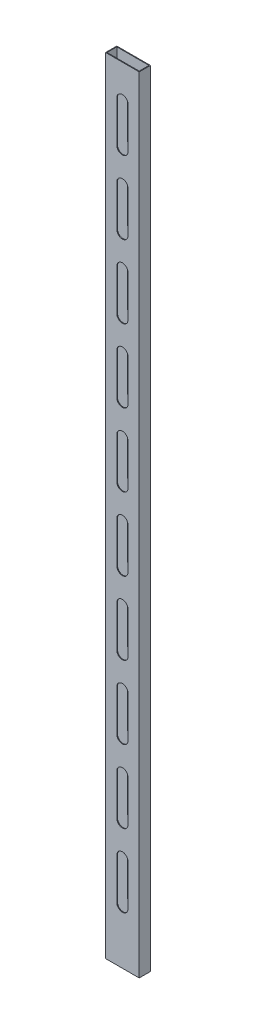
SolidWorks part; units mm, degrees
ref_plane "Front Plane" through (0, 0, 0) normal (0, 0, 1) x (1, 0, 0)
ref_plane "Top Plane" through (0, 0, 0) normal (0, 1, 0) x (1, 0, 0)
ref_plane "Right Plane" through (0, 0, 0) normal (1, 0, 0) x (0, 0, -1)
sketch "Sketch1" plane through (0, 0, 0) normal (0, 1, 0) x (1, 0, 0)
  line L1 (0, 0) -> (-76.2, 0)
  line L2 (0, 0) -> (0, 25.4)
  line L3 (0, 25.4) -> (-76.2, 25.4)
  line L4 (-76.2, 0) -> (-76.2, 25.4)
  line L5 (-74.6125, 1.5875) -> (-1.5875, 1.5875)
  line L6 (-74.6125, 1.5875) -> (-74.6125, 23.8125)
  line L7 (-74.6125, 23.8125) -> (-1.5875, 23.8125)
  line L8 (-1.5875, 1.5875) -> (-1.5875, 23.8125)
  dimension "D1" = 76.2
  dimension "D2" = 25.4
  dimension "D3" = 1.5875
  dimension "D4" = 1.5875
  dimension "D5" = 1.5875
  dimension "D6" = 1.5875
extrude "Boss-Extrude1" add sketch "Sketch1" along normal blind 1778
sketch "Sketch2" plane through (0, 0, 0) normal (0, 0, 1) x (1, 0, 0)
  line L0 (-38.1, 1701.8) -> (-38.1, 1608.6977) construction
  line L1 (-25.4, 1701.8) -> (-25.4, 1608.6977)
  line L2 (-50.8, 1701.8) -> (-50.8, 1608.6977)
  line L3 (0, 1778) -> (0, 0) construction
  line L4 (-76.2, 1778) -> (0, 1778) construction
  line L5 (-38.1, 1536.7) -> (-38.1, 1443.5977) construction
  line L6 (-25.4, 1536.7) -> (-25.4, 1443.5977)
  line L7 (-50.8, 1536.7) -> (-50.8, 1443.5977)
  line L8 (-38.1, 1371.6) -> (-38.1, 1278.4977) construction
  line L9 (-25.4, 1371.6) -> (-25.4, 1278.4977)
  line L10 (-50.8, 1371.6) -> (-50.8, 1278.4977)
  line L11 (-38.1, 1206.5) -> (-38.1, 1113.3977) construction
  line L12 (-25.4, 1206.5) -> (-25.4, 1113.3977)
  line L13 (-50.8, 1206.5) -> (-50.8, 1113.3977)
  line L14 (-38.1, 1041.4) -> (-38.1, 948.2977) construction
  line L15 (-25.4, 1041.4) -> (-25.4, 948.2977)
  line L16 (-50.8, 1041.4) -> (-50.8, 948.2977)
  line L17 (-38.1, 876.3) -> (-38.1, 783.1977) construction
  line L18 (-25.4, 876.3) -> (-25.4, 783.1977)
  line L19 (-50.8, 876.3) -> (-50.8, 783.1977)
  line L20 (-38.1, 711.2) -> (-38.1, 618.0977) construction
  line L21 (-25.4, 711.2) -> (-25.4, 618.0977)
  line L22 (-50.8, 711.2) -> (-50.8, 618.0977)
  line L23 (-38.1, 546.1) -> (-38.1, 452.9977) construction
  line L24 (-25.4, 546.1) -> (-25.4, 452.9977)
  line L25 (-50.8, 546.1) -> (-50.8, 452.9977)
  line L26 (-38.1, 381) -> (-38.1, 287.8977) construction
  line L27 (-25.4, 381) -> (-25.4, 287.8977)
  line L28 (-50.8, 381) -> (-50.8, 287.8977)
  line L29 (-38.1, 215.9) -> (-38.1, 122.7977) construction
  line L30 (-25.4, 215.9) -> (-25.4, 122.7977)
  line L31 (-50.8, 215.9) -> (-50.8, 122.7977)
  arc A0 (-25.4, 1701.8) -> (-50.8, 1701.8) centre (-38.1, 1701.8) ccw
  arc A1 (-50.8, 1608.6977) -> (-25.4, 1608.6977) centre (-38.1, 1608.6977) ccw
  arc A2 (-25.4, 1536.7) -> (-50.8, 1536.7) centre (-38.1, 1536.7) ccw
  arc A3 (-50.8, 1443.5977) -> (-25.4, 1443.5977) centre (-38.1, 1443.5977) ccw
  arc A4 (-25.4, 1371.6) -> (-50.8, 1371.6) centre (-38.1, 1371.6) ccw
  arc A5 (-50.8, 1278.4977) -> (-25.4, 1278.4977) centre (-38.1, 1278.4977) ccw
  arc A6 (-25.4, 1206.5) -> (-50.8, 1206.5) centre (-38.1, 1206.5) ccw
  arc A7 (-50.8, 1113.3977) -> (-25.4, 1113.3977) centre (-38.1, 1113.3977) ccw
  arc A8 (-25.4, 1041.4) -> (-50.8, 1041.4) centre (-38.1, 1041.4) ccw
  arc A9 (-50.8, 948.2977) -> (-25.4, 948.2977) centre (-38.1, 948.2977) ccw
  arc A10 (-25.4, 876.3) -> (-50.8, 876.3) centre (-38.1, 876.3) ccw
  arc A11 (-50.8, 783.1977) -> (-25.4, 783.1977) centre (-38.1, 783.1977) ccw
  arc A12 (-25.4, 711.2) -> (-50.8, 711.2) centre (-38.1, 711.2) ccw
  arc A13 (-50.8, 618.0977) -> (-25.4, 618.0977) centre (-38.1, 618.0977) ccw
  arc A14 (-25.4, 546.1) -> (-50.8, 546.1) centre (-38.1, 546.1) ccw
  arc A15 (-50.8, 452.9977) -> (-25.4, 452.9977) centre (-38.1, 452.9977) ccw
  arc A16 (-25.4, 381) -> (-50.8, 381) centre (-38.1, 381) ccw
  arc A17 (-50.8, 287.8977) -> (-25.4, 287.8977) centre (-38.1, 287.8977) ccw
  arc A18 (-25.4, 215.9) -> (-50.8, 215.9) centre (-38.1, 215.9) ccw
  arc A19 (-50.8, 122.7977) -> (-25.4, 122.7977) centre (-38.1, 122.7977) ccw
  point P2 (-38.1, 1655.2488)
  point P15 (-38.1, 1490.1488)
  point P22 (-38.1, 1325.0488)
  point P29 (-38.1, 1159.9488)
  point P36 (-38.1, 994.8488)
  point P43 (-38.1, 829.7488)
  point P50 (-38.1, 664.6488)
  point P57 (-38.1, 499.5488)
  point P64 (-38.1, 334.4488)
  point P71 (-38.1, 169.3488)
  dimension "D2" = 12.7
  dimension "D3" = 76.2
  dimension "D4" = 10
  dimension "D1" = 25.4
extrude "Cut-Extrude1" cut sketch "Sketch2" against normal through all
